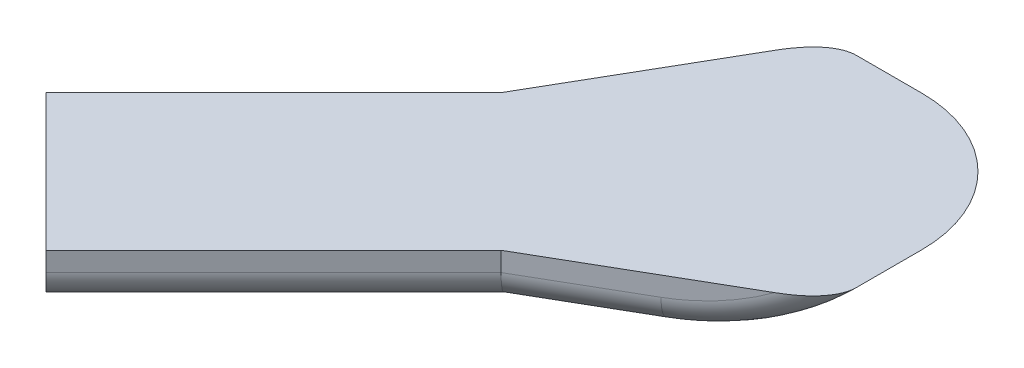
SolidWorks part; units mm, degrees
ref_plane "Front Plane" through (0, 0, 0) normal (0, 0, 1) x (1, 0, 0)
ref_plane "Top Plane" through (0, 0, 0) normal (0, 1, 0) x (1, 0, 0)
ref_plane "Right Plane" through (0, 0, 0) normal (1, 0, 0) x (0, 0, -1)
sketch "Sketch1" plane through (0, 0, 0) normal (0, 1, 0) x (1, 0, 0)
  line L0 (-17.5, 17.5) -> (-36.3331, -15.1199)
  line L1 (-17.5, 17.5) -> (-3.582, 17.5)
  line L2 (-17.5, 17.5) -> (-17.5, -17.5) construction
  line L3 (-17.5, -17.5) -> (17.5, -17.5) construction
  line L4 (17.5, -3.582) -> (17.5, -17.5)
  line L5 (-17.5, 17.5) -> (17.5, -17.5) construction
  line L6 (-17.5, -17.5) -> (17.5, 17.5) construction
  line L9 (-15.1199, -36.3331) -> (17.5, -17.5)
  line L10 (-36.3331, -15.1199) -> (-15.1199, -36.3331) construction
  line L11 (-25.7265, -25.7265) -> (-17.5, -17.5) construction
  line L12 (-36.3331, -15.1199) -> (-71.6885, -50.4752)
  line L13 (-71.6885, -50.4752) -> (-50.4752, -71.6885)
  line L14 (-50.4752, -71.6885) -> (-15.1199, -36.3331)
  line L15 (-61.0819, -61.0819) -> (-25.7265, -25.7265) construction
  arc A0 (-3.582, 17.5) -> (17.5, -3.582) centre (-3.582, -3.582) cw
  point P0 (0, 0)
  dimension "D3" = 21.082
  dimension "D1" = 30
  dimension "D2" = 35
  dimension "D4" = 30
  dimension "D5" = 30
  dimension "D6" = 50
extrude "Boss-Extrude1" add sketch "Sketch1" along normal blind 8
fillet "Fillet1" radius 27.432 2 edges at (-10.541, 0, -17.5) (17.5, 0, 10.541)
sketch "Sketch2" plane through (0, 8, 0) normal (0, 1, 0) x (1, 0, 0)
  line L0 (-3.582, 17.5) -> (-17.5, 17.5) construction
  line L1 (17.5, -17.5) -> (17.5, -3.582) construction
  circle A0 centre (-25.38, -4.51) radius 3
  circle A1 centre (-4.51, -25.38) radius 3
  dimension "D1" = 6
  dimension "D2" = 22.01
  dimension "D3" = 42.88
  dimension "D5" = 42.88
  dimension "22.01" = 22.01
extrude "Cut-Extrude1" [suppressed] cut sketch "Sketch2" against normal blind 6
fillet "Fillet3" radius 5 6 edges at (-22.6312, 2.0788, -8.6125) (8.6125, 2.0788, 22.6312) (-32.5061, 0, 8.4913) (-8.4913, 0, 32.5061) (-54.0108, 0, 32.7976) (-32.7976, 0, 54.0108)
